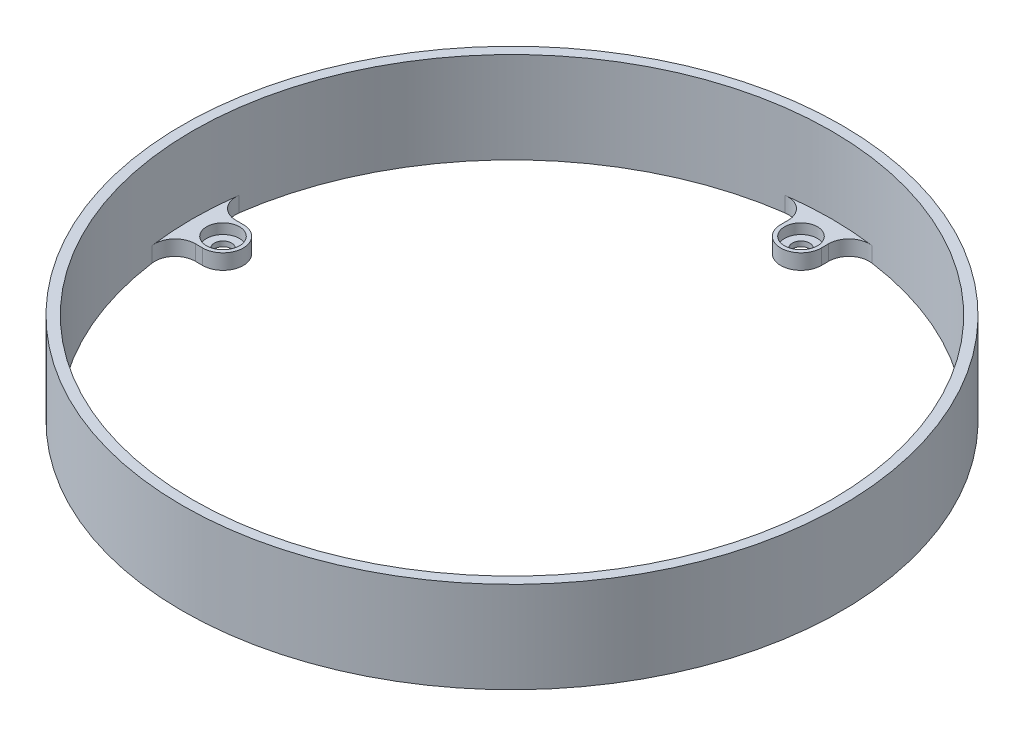
SolidWorks part; units mm, degrees
ref_plane "Front Plane" through (0, 0, 0) normal (0, 0, 1) x (1, 0, 0)
ref_plane "Top Plane" through (0, 0, 0) normal (0, 1, 0) x (1, 0, 0)
ref_plane "Right Plane" through (0, 0, 0) normal (1, 0, 0) x (0, 0, -1)
sketch "Sketch1" plane through (0, 0, 0) normal (0, 1, 0) x (1, 0, 0)
  circle A0 centre (0, 0) radius 63
  circle A1 centre (0, 0) radius 65
  dimension "D1" = 2
  dimension "D2" = 130
extrude "Boss-Extrude1" add sketch "Sketch1" along normal blind 18
sketch "Sketch2" plane through (0, 0, 0) normal (0, 1, 0) x (1, 0, 0)
  line L0 (-4, 58.4551) -> (-4, 57)
  line L1 (4, 58.4551) -> (4, 57)
  line L2 (58.4551, -4) -> (57, -4)
  line L3 (58.4551, 4) -> (57, 4)
  line L4 (-4, -58.4551) -> (-4, -57)
  line L5 (4, -58.4551) -> (4, -57)
  line L6 (-58.4551, 4) -> (-57, 4)
  line L7 (-58.4551, -4) -> (-57, -4)
  arc A0 (-8.5424, 62.4182) -> (-4, 58.4551) centre (-8, 58.4551) cw
  circle A2 centre (0, 0) radius 63 construction
  arc A3 (8.5424, 62.4182) -> (4, 58.4551) centre (8, 58.4551) ccw
  arc A4 (-4, 57) -> (4, 57) centre (0, 57) ccw
  arc A5 (-8.5424, 62.4182) -> (8.5424, 62.4182) centre (0, 0) cw
  arc A6 (62.4182, 8.5424) -> (62.4182, -8.5424) centre (0, 0) cw
  arc A7 (62.4182, -8.5424) -> (58.4551, -4) centre (58.4551, -8) ccw
  arc A8 (57, 4) -> (57, -4) centre (57, 0) ccw
  arc A9 (62.4182, 8.5424) -> (58.4551, 4) centre (58.4551, 8) cw
  arc A10 (8.5424, -62.4182) -> (-8.5424, -62.4182) centre (0, 0) cw
  arc A11 (-8.5424, -62.4182) -> (-4, -58.4551) centre (-8, -58.4551) ccw
  arc A12 (4, -57) -> (-4, -57) centre (0, -57) ccw
  arc A13 (8.5424, -62.4182) -> (4, -58.4551) centre (8, -58.4551) cw
  arc A14 (-62.4182, -8.5424) -> (-62.4182, 8.5424) centre (0, 0) cw
  arc A15 (-62.4182, 8.5424) -> (-58.4551, 4) centre (-58.4551, 8) ccw
  arc A16 (-57, -4) -> (-57, 4) centre (-57, 0) ccw
  arc A17 (-62.4182, -8.5424) -> (-58.4551, -4) centre (-58.4551, -8) cw
  point P13 (62.4182, -8)
  point P44 (0, 0)
  dimension "D1" = 4
  dimension "D2" = 57
extrude "Boss-Extrude2" add sketch "Sketch2" along normal blind 3
sketch "Sketch3" plane through (0, 3, 0) normal (0, 1, 0) x (1, 0, 0)
  point P0 (-57, 0)
  point P1 (0, 57)
  point P3 (57, 0)
  point P5 (0, -57)
  point P10 (-57, 0)
  point P12 (0, 57)
  point P14 (57, 0)
  point P16 (0, -57)
hole_wizard "CBORE for M3 SHCS1" positions "Sketch3" profile "Sketch7" counterbore size "M3" standard "ANSI Metric" end condition up to next
sketch "Sketch7" plane through (-57, 3, 0) normal (1, 0, 0) x (0, 0, 1)
  line L0 (0, 0) -> (0, 3)
  line L1 (0, 3) -> (1.7, 3)
  line L3 (1.7, 3) -> (1.7, 2)
  line L4 (1.7, 2) -> (3.25, 2)
  line L5 (3.25, 2) -> (3.25, 0)
  line L7 (3.25, 0) -> (0, 0)
  line L11 (0, -6.35) -> (0, 107.95) construction
  dimension "Thru Hole Dia." = 3.4
  dimension "Thru Hole Depth" = 3
  dimension "C'Bore Dia." = 6.5
  dimension "C'Bore Depth" = 2
